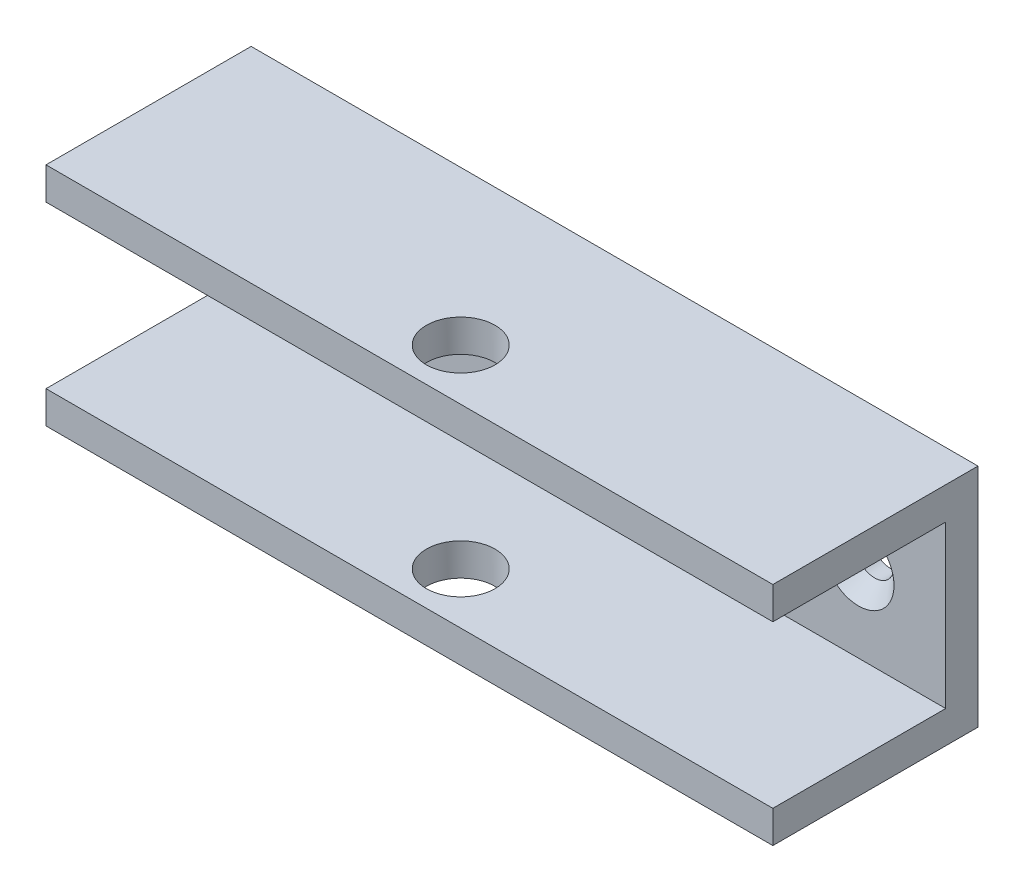
SolidWorks part; units mm, degrees
ref_plane "Front Plane" through (0, 0, 0) normal (0, 0, 1) x (1, 0, 0)
ref_plane "Top Plane" through (0, 0, 0) normal (0, 1, 0) x (1, 0, 0)
ref_plane "Right Plane" through (0, 0, 0) normal (1, 0, 0) x (0, 0, -1)
sketch "Sketch1" plane through (0, 0, 0) normal (0, 0, 1) x (1, 0, 0)
  line L1 (-22.5, -7) -> (22.5, -7)
  line L2 (-22.5, -7) -> (-22.5, 7)
  line L3 (-22.5, 7) -> (22.5, 7)
  line L4 (22.5, -7) -> (22.5, 7)
  line L5 (-22.5, -7) -> (22.5, 7) construction
  line L6 (-22.5, 7) -> (22.5, -7) construction
  point P0 (0, 0)
  dimension "D1" = 45
  dimension "D2" = 14
extrude "Boss-Extrude1" add sketch "Sketch1" along normal blind 12.7
sketch "Sketch2" plane through (0, 0, 12.7) normal (0, 0, 1) x (1, 0, 0)
  line L0 (22.5, -7) -> (22.5, 7) construction
  line L1 (-22.5, -5) -> (22.5, -5)
  line L2 (-22.5, -5) -> (-22.5, 5)
  line L3 (-22.5, 5) -> (22.5, 5)
  line L4 (22.5, -5) -> (22.5, 5)
  line L5 (-22.5, -5) -> (22.5, 5) construction
  line L6 (-22.5, 5) -> (22.5, -5) construction
  line L7 (22.5, 7) -> (-22.5, 7) construction
  point P0 (0, 0)
  dimension "D1" = 2
extrude "Cut-Extrude1" cut sketch "Sketch2" against normal blind 10.7
hole_wizard "CSK for M2 Flat Head Machine Screw1" positions "3DSketch1" profile "Sketch3" countersink size "M2" standard "ANSI Metric" end condition through all
sketch3d "3DSketch1"
  line L0 (-22.5, 5, 2) -> (-22.5, -5, 2) construction
  line L1 (22.5, -5, 2) -> (22.5, 5, 2) construction
  point P0 (-17.1, 0, 2)
  point P2 (17.1, 0, 2)
  point P11 (-22.5, 0, 2)
  dimension "D1" = 5.4
  dimension "D2" = 5.4
sketch "Sketch3" plane through (-17.1, 0, 2) normal (1, 0, 0) x (0, -1, 0)
  line L0 (0, 0) -> (0, 2)
  line L1 (0, 2) -> (1.2, 2)
  line L2 (1.2, 2) -> (1.2, 1)
  line L3 (1.2, 1) -> (2.2, 0)
  line L5 (2.2, 0) -> (0, 0)
  line L6 (-1.2, 1) -> (-2.2, 0) construction
  line L11 (0, -6.35) -> (0, 107.95) construction
  dimension "Thru Hole Dia." = 2.4
  dimension "Thru Hole Depth" = 2
  dimension "Near C'Sink Dia." = 4.4
  dimension "Near C'Sink Angle" = 90
sketch "Sketch5" plane through (0, 7, 0) normal (0, 1, 0) x (1, 0, 0)
  line L1 (-22.5, -12.7) -> (-22.5, 0) construction
  line L3 (22.5, 0) -> (-22.5, 0) construction
  circle A0 centre (0, -9.525) radius 2.125
  dimension "D1" = 4.25
  dimension "D2" = 22.5
  dimension "D3" = 9.525
extrude "Cut-Extrude2" cut sketch "Sketch5" against normal through all both and the other way through all
ref_axis "DoorBracketPinAxis" through (0, 5, 9.525) along (0, 1, 0)
ref_plane "DoorBracketPinPlane" through (0, 0, 9.525) normal (0, 0, -1) x (-1, 0, 0)
ref_plane "DoorBracketLineofAction" through (0, 0, 0) normal (1, 0, 0) x (0, 0, -1)
